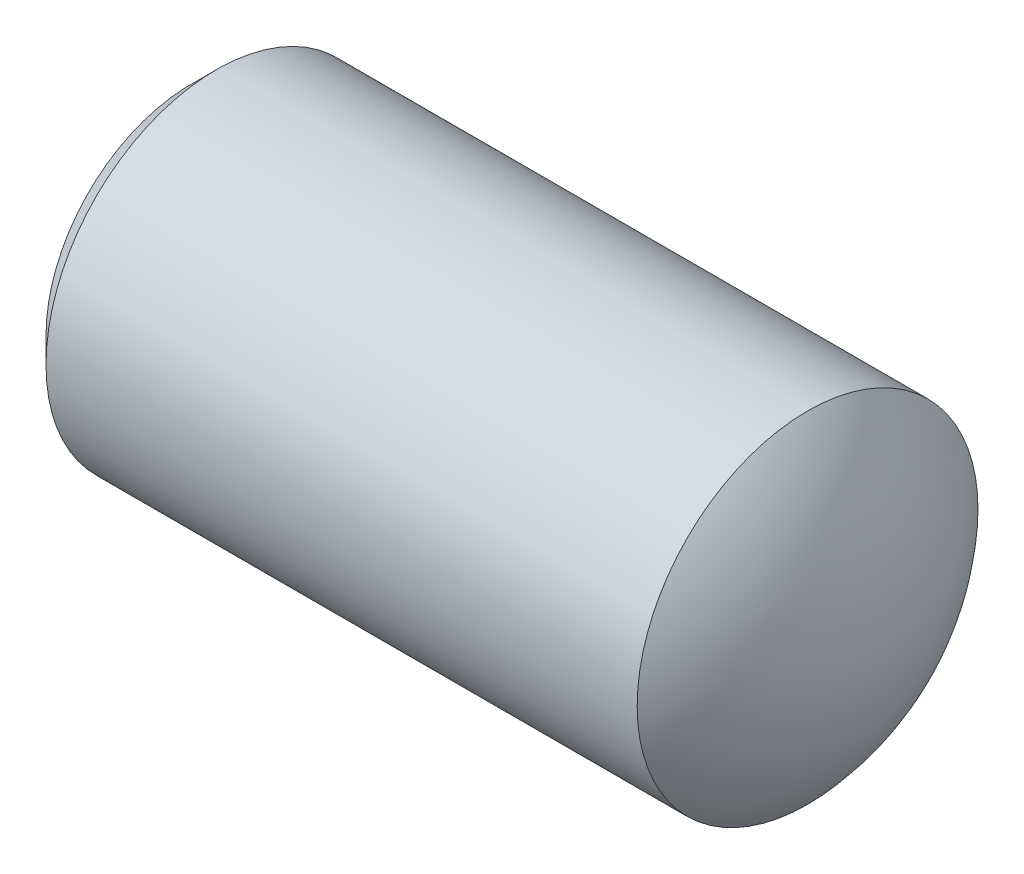
SolidWorks part; units mm, degrees
revolve "BaseBody" add sketch "BodySke" angle 360 about L5 other way angle 60
sketch "BodySke" plane through (0, 0, 0) normal (0, 0, 1) x (1, 0, 0)
  line L0 (0, 0) -> (0, 10.8102)
  line L1 (0, 10.8102) -> (1.8898, 12.7)
  line L2 (1.8898, 12.7) -> (45.949, 12.7)
  line L3 (2.1082, 15.875) -> (2.1082, -3.175) construction
  line L4 (50.8, 0) -> (0, 0)
  line L5 (-12.7, 0) -> (88.9, 0) construction
  line L8 (0, -10.8102) -> (1.8898, -12.7) construction
  arc A0 (50.8, 0) -> (45.949, 12.7) centre (31.75, 0) ccw
  dimension "Length" = 50.8
  dimension "Diameter" = 25.4
cosmetic thread "ThreadCosmetic" [suppressed] parameters "Thread_minor"=21.6205
ref_plane "Plane1" through (0, 0, 0) normal (0, 0, 1) x (1, 0, 0)
ref_plane "Plane2" through (0, 0, 0) normal (0, 1, 0) x (1, 0, 0)
ref_plane "Plane3" through (0, 0, 0) normal (1, 0, 0) x (0, 0, -1)
sketch "Sketch2" plane through (0, 0, 0) normal (-1, 0, 0) x (0, 0, 1)
  line L0 (4.1208, 7.1374) -> (-4.1208, 7.1374)
  line L1 (-4.1208, 7.1374) -> (-8.2416, 0)
  line L2 (4.1208, 7.1374) -> (8.2416, 0)
  line L3 (4.1208, -7.1374) -> (8.2416, 0)
  line L4 (4.1208, -7.1374) -> (-4.1208, -7.1374)
  line L5 (-4.1208, -7.1374) -> (-8.2416, 0)
  dimension "D2" = 7.1374
  dimension "D3" = 7.1374
extrude "Hex" cut sketch "Sketch2" against normal blind 14.2748
sketch "Sketch4" plane through (0, 4.7709, -0.5249) normal (-1, 0, 0) x (0, 0, 1)
  line L0 (0.5249, -4.7709) -> (10.6976, -4.7709)
  line L1 (0.5249, -4.7709) -> (6.6732, -1.2211) construction
  line L2 (0.5249, -4.7709) -> (5.6112, 4.0389)
  line L3 (8.9666, -2.6687) -> (10.2861, -1.9069)
  line L4 (6.5663, 1.4888) -> (7.8858, 2.2506)
  arc A0 (8.9666, -2.6687) -> (6.5663, 1.4888) centre (0.5249, -4.7709) ccw
  arc A1 (10.6976, -4.7709) -> (10.2861, -1.9069) centre (0.5249, -4.7709) ccw
  arc A2 (5.6112, 4.0389) -> (7.8858, 2.2506) centre (0.5249, -4.7709) cw
  circle A3 centre (0.5249, -4.7709) radius 8.6995 construction
  circle A4 centre (0.5249, -4.7709) radius 10.1727 construction
  dimension "Spline_n_dim" = 17.399
  dimension "Spline_m_dim" = 20.3454
  dimension "D1" = 30
  dimension "Spline_p_dim" = 4.8006
  dimension "D3" = 2.4003
extrude "Spline" [suppressed] cut sketch "Sketch4" against normal blind 12.7
pattern_circular "CirPattern1" [suppressed] count 6 every 60 about axis through (-12.7, 0, 0) along (1, 0, 0)
sketch "ThdSchSke" plane through (0, 0, 0) normal (0, 0, 1) x (1, 0, 0)
  line L0 (1.8898, -10.8102) -> (0.5665, -12.7)
  line L1 (1.8898, -10.8102) -> (3.213, -12.7)
  line L2 (3.213, -12.7) -> (3.213, -15.875)
  line L3 (-3.175, 0) -> (5.1513, 0) construction
  line L4 (1.8898, 12.7) -> (1.8898, -12.7) construction
  line L5 (3.213, -15.875) -> (0.5665, -15.875)
  line L6 (0.5665, -15.875) -> (0.5665, -12.7)
  dimension "Thread_minor" = 21.6205
  dimension "Diameter" = 25.4
revolve "ThreadSchematic" [suppressed] cut sketch "ThdSchSke" angle 360 about L3
pattern_linear "ThdSchPat" [suppressed]
equation "\"D2@Sketch2\" = \"Hex_size@Sketch2\" / 2"
equation "\"D3@Sketch2\" = \"Hex_size@Sketch2\" / 2"
equation "\"Thread_minor@ThreadCosmetic\" = \"Minor_dia@BodySke\""
equation "\"D1@Sketch4\" = \"Spline_a_dim@Sketch4\" / 2"
equation "\"D3@Sketch4\" = \"Spline_p_dim@Sketch4\" / 2"
equation "\"D2@CirPattern1\" = \"Spline_a_dim@Sketch4\""
equation "\"Num_teeth@CirPattern1\" = 360 / \"D2@CirPattern1\""
equation "\"Thread_minor@ThdSchSke\" = \"Thread_minor@ThreadCosmetic\""
equation "\"Diameter@ThdSchSke\" = \"Diameter@BodySke\""
equation "\"Overcut@ThdSchSke\" = \"Diameter@BodySke\" * 1.25"
equation "\"Num_threads@ThdSchPat\" = int( (\"Length@BodySke\" - ( ( ( \"Diameter@BodySke\" - \"Minor_dia@BodySke\" ) * 0.5 ) / tan( \"Drive_ch_ang@BodySke\" * 0.017453292 ) ) - ( \"Oval_radius@BodySke\" - sqr ( ( \"Oval_radius@BodySke\" * \"Oval_radius@BodySke\" ) - ( ( \"Diameter@BodySke\" * 0.5 ) * ( \"Diameter@BodySke\" * 0.5 ) ) ) ) ) / \"Advance@BodySke\" + 0.999 )  + 1"
equation "\"Advance@ThdSchPat\" = (\"Length@BodySke\" - ( ( ( \"Diameter@BodySke\" - \"Minor_dia@BodySke\" ) * 0.5 ) / tan( \"Drive_ch_ang@BodySke\" * 0.017453292 ) ) - ( \"Oval_radius@BodySke\" - sqr ( ( \"Oval_radius@BodySke\" * \"Oval_radius@BodySke\" ) - ( ( \"Diameter@BodySke\" * 0.5 ) * ( \"Diameter@BodySke\" * 0.5 ) ) ) ) ) /  (\"Num_threads@ThdSchPat\" - 1) 'relax it"
equation "' \"Num_threads@ThdSchPat\" = \"Num_threads@ThdSchPat\" - sgn( \"Num_threads@ThdSchPat\" - 1) '---chamfered tips only---"
